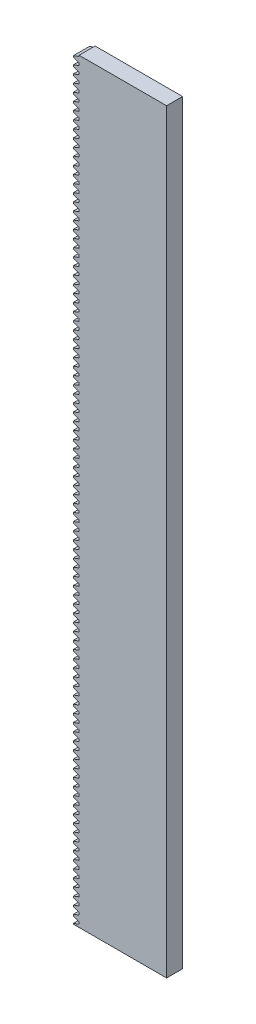
SolidWorks part; units mm, degrees
ref_plane "Front Plane" through (0, 0, 0) normal (0, 0, 1) x (1, 0, 0)
ref_plane "Top Plane" through (0, 0, 0) normal (0, 1, 0) x (1, 0, 0)
ref_plane "Right Plane" through (0, 0, 0) normal (1, 0, 0) x (0, 0, -1)
sketch "Sketch1" plane through (0, 0, 0) normal (0, 0, 1) x (1, 0, 0)
  line L0 (-9.5, -73.594) -> (-8.375, -74.0034)
  line L1 (-9, -75) -> (9, -75) construction
  line L2 (-9, -75) -> (-9, 75) construction
  line L3 (-9, 75) -> (9, 75) construction
  line L4 (9, -75) -> (9, 75) construction
  line L5 (-9, -75) -> (9, 75) construction
  line L6 (-9, 75) -> (9, -75) construction
  line L7 (-8.375, -74.0034) -> (-8.375, -74.4479)
  line L8 (-8.375, -74.4479) -> (-9.5, -74.8573)
  line L9 (-9.5, -74.8573) -> (-9.5, -75)
  line L10 (-9.5, -75) -> (9, -75)
  line L11 (9, -75) -> (9, 75)
  line L12 (9, 75) -> (-8.375, 75)
  line L13 (-8.375, 75) -> (-8.375, 74.7778)
  line L14 (-8.375, 74.7778) -> (-9.5, 74.3683)
  line L15 (-9.5, 74.3683) -> (-9.5, 74.0609)
  line L16 (-9.5, 74.0609) -> (-8.375, 73.6514)
  line L17 (-8.375, 73.6514) -> (-8.375, 73.207)
  line L18 (-8.375, 73.207) -> (-9.5, 72.7975)
  line L19 (-9.5, 72.7975) -> (-9.5, 72.4901)
  line L20 (-9.5, 72.4901) -> (-8.375, 72.0806)
  line L21 (-8.375, 72.0806) -> (-8.375, 71.6362)
  line L22 (-8.375, 71.6362) -> (-9.5, 71.2267)
  line L23 (-9.5, 71.2267) -> (-9.5, 70.9193)
  line L24 (-9.5, 70.9193) -> (-8.375, 70.5098)
  line L25 (-8.375, 70.5098) -> (-8.375, 70.0654)
  line L26 (-8.375, 70.0654) -> (-9.5, 69.6559)
  line L27 (-9.5, 69.6559) -> (-9.5, 69.3485)
  line L28 (-9.5, 69.3485) -> (-8.375, 68.939)
  line L29 (-8.375, 68.939) -> (-8.375, 68.4946)
  line L30 (-8.375, 68.4946) -> (-9.5, 68.0851)
  line L31 (-9.5, 68.0851) -> (-9.5, 67.7777)
  line L32 (-9.5, 67.7777) -> (-8.375, 67.3682)
  line L33 (-8.375, 67.3682) -> (-8.375, 66.9238)
  line L34 (-8.375, 66.9238) -> (-9.5, 66.5143)
  line L35 (-9.5, 66.5143) -> (-9.5, 66.2069)
  line L36 (-9.5, 66.2069) -> (-8.375, 65.7974)
  line L37 (-8.375, 65.7974) -> (-8.375, 65.353)
  line L38 (-8.375, 65.353) -> (-9.5, 64.9435)
  line L39 (-9.5, 64.9435) -> (-9.5, 64.6361)
  line L40 (-9.5, 64.6361) -> (-8.375, 64.2266)
  line L41 (-8.375, 64.2266) -> (-8.375, 63.7822)
  line L42 (-8.375, 63.7822) -> (-9.5, 63.3727)
  line L43 (-9.5, 63.3727) -> (-9.5, 63.0653)
  line L44 (-9.5, 63.0653) -> (-8.375, 62.6558)
  line L45 (-8.375, 62.6558) -> (-8.375, 62.2114)
  line L46 (-8.375, 62.2114) -> (-9.5, 61.8019)
  line L47 (-9.5, 61.8019) -> (-9.5, 61.4945)
  line L48 (-9.5, 61.4945) -> (-8.375, 61.0851)
  line L49 (-8.375, 61.0851) -> (-8.375, 60.6406)
  line L50 (-8.375, 60.6406) -> (-9.5, 60.2311)
  line L51 (-9.5, 60.2311) -> (-9.5, 59.9237)
  line L52 (-9.5, 59.9237) -> (-8.375, 59.5143)
  line L53 (-8.375, 59.5143) -> (-8.375, 59.0698)
  line L54 (-8.375, 59.0698) -> (-9.5, 58.6604)
  line L55 (-9.5, 58.6604) -> (-9.5, 58.3529)
  line L56 (-9.5, 58.3529) -> (-8.375, 57.9435)
  line L57 (-8.375, 57.9435) -> (-8.375, 57.499)
  line L58 (-8.375, 57.499) -> (-9.5, 57.0896)
  line L59 (-9.5, 57.0896) -> (-9.5, 56.7821)
  line L60 (-9.5, 56.7821) -> (-8.375, 56.3727)
  line L61 (-8.375, 56.3727) -> (-8.375, 55.9282)
  line L62 (-8.375, 55.9282) -> (-9.5, 55.5188)
  line L63 (-9.5, 55.5188) -> (-9.5, 55.2113)
  line L64 (-9.5, 55.2113) -> (-8.375, 54.8019)
  line L65 (-8.375, 54.8019) -> (-8.375, 54.3574)
  line L66 (-8.375, 54.3574) -> (-9.5, 53.948)
  line L67 (-9.5, 53.948) -> (-9.5, 53.6405)
  line L68 (-9.5, 53.6405) -> (-8.375, 53.2311)
  line L69 (-8.375, 53.2311) -> (-8.375, 52.7866)
  line L70 (-8.375, 52.7866) -> (-9.5, 52.3772)
  line L71 (-9.5, 52.3772) -> (-9.5, 52.0697)
  line L72 (-9.5, 52.0697) -> (-8.375, 51.6603)
  line L73 (-8.375, 51.6603) -> (-8.375, 51.2158)
  line L74 (-8.375, 51.2158) -> (-9.5, 50.8064)
  line L75 (-9.5, 50.8064) -> (-9.5, 50.4989)
  line L76 (-9.5, 50.4989) -> (-8.375, 50.0895)
  line L77 (-8.375, 50.0895) -> (-8.375, 49.645)
  line L78 (-8.375, 49.645) -> (-9.5, 49.2356)
  line L79 (-9.5, 49.2356) -> (-9.5, 48.9281)
  line L80 (-9.5, 48.9281) -> (-8.375, 48.5187)
  line L81 (-8.375, 48.5187) -> (-8.375, 48.0742)
  line L82 (-8.375, 48.0742) -> (-9.5, 47.6648)
  line L83 (-9.5, 47.6648) -> (-9.5, 47.3574)
  line L84 (-9.5, 47.3574) -> (-8.375, 46.9479)
  line L85 (-8.375, 46.9479) -> (-8.375, 46.5034)
  line L86 (-8.375, 46.5034) -> (-9.5, 46.094)
  line L87 (-9.5, 46.094) -> (-9.5, 45.7866)
  line L88 (-9.5, 45.7866) -> (-8.375, 45.3771)
  line L89 (-8.375, 45.3771) -> (-8.375, 44.9327)
  line L90 (-8.375, 44.9327) -> (-9.5, 44.5232)
  line L91 (-9.5, 44.5232) -> (-9.5, 44.2158)
  line L92 (-9.5, 44.2158) -> (-8.375, 43.8063)
  line L93 (-8.375, 43.8063) -> (-8.375, 43.3619)
  line L94 (-8.375, 43.3619) -> (-9.5, 42.9524)
  line L95 (-9.5, 42.9524) -> (-9.5, 42.645)
  line L96 (-9.5, 42.645) -> (-8.375, 42.2355)
  line L97 (-8.375, 42.2355) -> (-8.375, 41.7911)
  line L98 (-8.375, 41.7911) -> (-9.5, 41.3816)
  line L99 (-9.5, 41.3816) -> (-9.5, 41.0742)
  line L100 (-9.5, 41.0742) -> (-8.375, 40.6647)
  line L101 (-8.375, 40.6647) -> (-8.375, 40.2203)
  line L102 (-8.375, 40.2203) -> (-9.5, 39.8108)
  line L103 (-9.5, 39.8108) -> (-9.5, 39.5034)
  line L104 (-9.5, 39.5034) -> (-8.375, 39.0939)
  line L105 (-8.375, 39.0939) -> (-8.375, 38.6495)
  line L106 (-8.375, 38.6495) -> (-9.5, 38.24)
  line L107 (-9.5, 38.24) -> (-9.5, 37.9326)
  line L108 (-9.5, 37.9326) -> (-8.375, 37.5231)
  line L109 (-8.375, 37.5231) -> (-8.375, 37.0787)
  line L110 (-8.375, 37.0787) -> (-9.5, 36.6692)
  line L111 (-9.5, 36.6692) -> (-9.5, 36.3618)
  line L112 (-9.5, 36.3618) -> (-8.375, 35.9523)
  line L113 (-8.375, 35.9523) -> (-8.375, 35.5079)
  line L114 (-8.375, 35.5079) -> (-9.5, 35.0984)
  line L115 (-9.5, 35.0984) -> (-9.5, 34.791)
  line L116 (-9.5, 34.791) -> (-8.375, 34.3815)
  line L117 (-8.375, 34.3815) -> (-8.375, 33.9371)
  line L118 (-8.375, 33.9371) -> (-9.5, 33.5276)
  line L119 (-9.5, 33.5276) -> (-9.5, 33.2202)
  line L120 (-9.5, 33.2202) -> (-8.375, 32.8107)
  line L121 (-8.375, 32.8107) -> (-8.375, 32.3663)
  line L122 (-8.375, 32.3663) -> (-9.5, 31.9568)
  line L123 (-9.5, 31.9568) -> (-9.5, 31.6494)
  line L124 (-9.5, 31.6494) -> (-8.375, 31.2399)
  line L125 (-8.375, 31.2399) -> (-8.375, 30.7955)
  line L126 (-8.375, 30.7955) -> (-9.5, 30.386)
  line L127 (-9.5, 30.386) -> (-9.5, 30.0786)
  line L128 (-9.5, 30.0786) -> (-8.375, 29.6691)
  line L129 (-8.375, 29.6691) -> (-8.375, 29.2247)
  line L130 (-8.375, 29.2247) -> (-9.5, 28.8152)
  line L131 (-9.5, 28.8152) -> (-9.5, 28.5078)
  line L132 (-9.5, 28.5078) -> (-8.375, 28.0983)
  line L133 (-8.375, 28.0983) -> (-8.375, 27.6539)
  line L134 (-8.375, 27.6539) -> (-9.5, 27.2444)
  line L135 (-9.5, 27.2444) -> (-9.5, 26.937)
  line L136 (-9.5, 26.937) -> (-8.375, 26.5275)
  line L137 (-8.375, 26.5275) -> (-8.375, 26.0831)
  line L138 (-8.375, 26.0831) -> (-9.5, 25.6736)
  line L139 (-9.5, 25.6736) -> (-9.5, 25.3662)
  line L140 (-9.5, 25.3662) -> (-8.375, 24.9567)
  line L141 (-8.375, 24.9567) -> (-8.375, 24.5123)
  line L142 (-8.375, 24.5123) -> (-9.5, 24.1028)
  line L143 (-9.5, 24.1028) -> (-9.5, 23.7954)
  line L144 (-9.5, 23.7954) -> (-8.375, 23.3859)
  line L145 (-8.375, 23.3859) -> (-8.375, 22.9415)
  line L146 (-8.375, 22.9415) -> (-9.5, 22.532)
  line L147 (-9.5, 22.532) -> (-9.5, 22.2246)
  line L148 (-9.5, 22.2246) -> (-8.375, 21.8151)
  line L149 (-8.375, 21.8151) -> (-8.375, 21.3707)
  line L150 (-8.375, 21.3707) -> (-9.5, 20.9612)
  line L151 (-9.5, 20.9612) -> (-9.5, 20.6538)
  line L152 (-9.5, 20.6538) -> (-8.375, 20.2443)
  line L153 (-8.375, 20.2443) -> (-8.375, 19.7999)
  line L154 (-8.375, 19.7999) -> (-9.5, 19.3904)
  line L155 (-9.5, 19.3904) -> (-9.5, 19.083)
  line L156 (-9.5, 19.083) -> (-8.375, 18.6735)
  line L157 (-8.375, 18.6735) -> (-8.375, 18.2291)
  line L158 (-8.375, 18.2291) -> (-9.5, 17.8196)
  line L159 (-9.5, 17.8196) -> (-9.5, 17.5122)
  line L160 (-9.5, 17.5122) -> (-8.375, 17.1028)
  line L161 (-8.375, 17.1028) -> (-8.375, 16.6583)
  line L162 (-8.375, 16.6583) -> (-9.5, 16.2489)
  line L163 (-9.5, 16.2489) -> (-9.5, 15.9414)
  line L164 (-9.5, 15.9414) -> (-8.375, 15.532)
  line L165 (-8.375, 15.532) -> (-8.375, 15.0875)
  line L166 (-8.375, 15.0875) -> (-9.5, 14.6781)
  line L167 (-9.5, 14.6781) -> (-9.5, 14.3706)
  line L168 (-9.5, 14.3706) -> (-8.375, 13.9612)
  line L169 (-8.375, 13.9612) -> (-8.375, 13.5167)
  line L170 (-8.375, 13.5167) -> (-9.5, 13.1073)
  line L171 (-9.5, 13.1073) -> (-9.5, 12.7998)
  line L172 (-9.5, 12.7998) -> (-8.375, 12.3904)
  line L173 (-8.375, 12.3904) -> (-8.375, 11.9459)
  line L174 (-8.375, 11.9459) -> (-9.5, 11.5365)
  line L175 (-9.5, 11.5365) -> (-9.5, 11.229)
  line L176 (-9.5, 11.229) -> (-8.375, 10.8196)
  line L177 (-8.375, 10.8196) -> (-8.375, 10.3751)
  line L178 (-8.375, 10.3751) -> (-9.5, 9.9657)
  line L179 (-9.5, 9.9657) -> (-9.5, 9.6582)
  line L180 (-9.5, 9.6582) -> (-8.375, 9.2488)
  line L181 (-8.375, 9.2488) -> (-8.375, 8.8043)
  line L182 (-8.375, 8.8043) -> (-9.5, 8.3949)
  line L183 (-9.5, 8.3949) -> (-9.5, 8.0874)
  line L184 (-9.5, 8.0874) -> (-8.375, 7.678)
  line L185 (-8.375, 7.678) -> (-8.375, 7.2335)
  line L186 (-8.375, 7.2335) -> (-9.5, 6.8241)
  line L187 (-9.5, 6.8241) -> (-9.5, 6.5166)
  line L188 (-9.5, 6.5166) -> (-8.375, 6.1072)
  line L189 (-8.375, 6.1072) -> (-8.375, 5.6627)
  line L190 (-8.375, 5.6627) -> (-9.5, 5.2533)
  line L191 (-9.5, 5.2533) -> (-9.5, 4.9458)
  line L192 (-9.5, 4.9458) -> (-8.375, 4.5364)
  line L193 (-8.375, 4.5364) -> (-8.375, 4.0919)
  line L194 (-8.375, 4.0919) -> (-9.5, 3.6825)
  line L195 (-9.5, 3.6825) -> (-9.5, 3.3751)
  line L196 (-9.5, 3.3751) -> (-8.375, 2.9656)
  line L197 (-8.375, 2.9656) -> (-8.375, 2.5212)
  line L198 (-8.375, 2.5212) -> (-9.5, 2.1117)
  line L199 (-9.5, 2.1117) -> (-9.5, 1.8043)
  line L200 (-9.5, 1.8043) -> (-8.375, 1.3948)
  line L201 (-8.375, 1.3948) -> (-8.375, 0.9504)
  line L202 (-8.375, 0.9504) -> (-9.5, 0.5409)
  line L203 (-9.5, 0.5409) -> (-9.5, 0.2335)
  line L204 (-9.5, 0.2335) -> (-8.375, -0.176)
  line L205 (-8.375, -0.176) -> (-8.375, -0.6204)
  line L206 (-8.375, -0.6204) -> (-9.5, -1.0299)
  line L207 (-9.5, -1.0299) -> (-9.5, -1.3373)
  line L208 (-9.5, -1.3373) -> (-8.375, -1.7468)
  line L209 (-8.375, -1.7468) -> (-8.375, -2.1912)
  line L210 (-8.375, -2.1912) -> (-9.5, -2.6007)
  line L211 (-9.5, -2.6007) -> (-9.5, -2.9081)
  line L212 (-9.5, -2.9081) -> (-8.375, -3.3176)
  line L213 (-8.375, -3.3176) -> (-8.375, -3.762)
  line L214 (-8.375, -3.762) -> (-9.5, -4.1715)
  line L215 (-9.5, -4.1715) -> (-9.5, -4.4789)
  line L216 (-9.5, -4.4789) -> (-8.375, -4.8884)
  line L217 (-8.375, -4.8884) -> (-8.375, -5.3328)
  line L218 (-8.375, -5.3328) -> (-9.5, -5.7423)
  line L219 (-9.5, -5.7423) -> (-9.5, -6.0497)
  line L220 (-9.5, -6.0497) -> (-8.375, -6.4592)
  line L221 (-8.375, -6.4592) -> (-8.375, -6.9036)
  line L222 (-8.375, -6.9036) -> (-9.5, -7.3131)
  line L223 (-9.5, -7.3131) -> (-9.5, -7.6205)
  line L224 (-9.5, -7.6205) -> (-8.375, -8.03)
  line L225 (-8.375, -8.03) -> (-8.375, -8.4744)
  line L226 (-8.375, -8.4744) -> (-9.5, -8.8839)
  line L227 (-9.5, -8.8839) -> (-9.5, -9.1913)
  line L228 (-9.5, -9.1913) -> (-8.375, -9.6008)
  line L229 (-8.375, -9.6008) -> (-8.375, -10.0452)
  line L230 (-8.375, -10.0452) -> (-9.5, -10.4547)
  line L231 (-9.5, -10.4547) -> (-9.5, -10.7621)
  line L232 (-9.5, -10.7621) -> (-8.375, -11.1716)
  line L233 (-8.375, -11.1716) -> (-8.375, -11.616)
  line L234 (-8.375, -11.616) -> (-9.5, -12.0255)
  line L235 (-9.5, -12.0255) -> (-9.5, -12.3329)
  line L236 (-9.5, -12.3329) -> (-8.375, -12.7424)
  line L237 (-8.375, -12.7424) -> (-8.375, -13.1868)
  line L238 (-8.375, -13.1868) -> (-9.5, -13.5963)
  line L239 (-9.5, -13.5963) -> (-9.5, -13.9037)
  line L240 (-9.5, -13.9037) -> (-8.375, -14.3132)
  line L241 (-8.375, -14.3132) -> (-8.375, -14.7576)
  line L242 (-8.375, -14.7576) -> (-9.5, -15.1671)
  line L243 (-9.5, -15.1671) -> (-9.5, -15.4745)
  line L244 (-9.5, -15.4745) -> (-8.375, -15.884)
  line L245 (-8.375, -15.884) -> (-8.375, -16.3284)
  line L246 (-8.375, -16.3284) -> (-9.5, -16.7379)
  line L247 (-9.5, -16.7379) -> (-9.5, -17.0453)
  line L248 (-9.5, -17.0453) -> (-8.375, -17.4548)
  line L249 (-8.375, -17.4548) -> (-8.375, -17.8992)
  line L250 (-8.375, -17.8992) -> (-9.5, -18.3087)
  line L251 (-9.5, -18.3087) -> (-9.5, -18.6161)
  line L252 (-9.5, -18.6161) -> (-8.375, -19.0256)
  line L253 (-8.375, -19.0256) -> (-8.375, -19.47)
  line L254 (-8.375, -19.47) -> (-9.5, -19.8795)
  line L255 (-9.5, -19.8795) -> (-9.5, -20.1869)
  line L256 (-9.5, -20.1869) -> (-8.375, -20.5964)
  line L257 (-8.375, -20.5964) -> (-8.375, -21.0408)
  line L258 (-8.375, -21.0408) -> (-9.5, -21.4503)
  line L259 (-9.5, -21.4503) -> (-9.5, -21.7577)
  line L260 (-9.5, -21.7577) -> (-8.375, -22.1672)
  line L261 (-8.375, -22.1672) -> (-8.375, -22.6116)
  line L262 (-8.375, -22.6116) -> (-9.5, -23.0211)
  line L263 (-9.5, -23.0211) -> (-9.5, -23.3285)
  line L264 (-9.5, -23.3285) -> (-8.375, -23.738)
  line L265 (-8.375, -23.738) -> (-8.375, -24.1824)
  line L266 (-8.375, -24.1824) -> (-9.5, -24.5919)
  line L267 (-9.5, -24.5919) -> (-9.5, -24.8993)
  line L268 (-9.5, -24.8993) -> (-8.375, -25.3087)
  line L269 (-8.375, -25.3087) -> (-8.375, -25.7532)
  line L270 (-8.375, -25.7532) -> (-9.5, -26.1626)
  line L271 (-9.5, -26.1626) -> (-9.5, -26.4701)
  line L272 (-9.5, -26.4701) -> (-8.375, -26.8795)
  line L273 (-8.375, -26.8795) -> (-8.375, -27.324)
  line L274 (-8.375, -27.324) -> (-9.5, -27.7334)
  line L275 (-9.5, -27.7334) -> (-9.5, -28.0409)
  line L276 (-9.5, -28.0409) -> (-8.375, -28.4503)
  line L277 (-8.375, -28.4503) -> (-8.375, -28.8948)
  line L278 (-8.375, -28.8948) -> (-9.5, -29.3042)
  line L279 (-9.5, -29.3042) -> (-9.5, -29.6117)
  line L280 (-9.5, -29.6117) -> (-8.375, -30.0211)
  line L281 (-8.375, -30.0211) -> (-8.375, -30.4656)
  line L282 (-8.375, -30.4656) -> (-9.5, -30.875)
  line L283 (-9.5, -30.875) -> (-9.5, -31.1825)
  line L284 (-9.5, -31.1825) -> (-8.375, -31.5919)
  line L285 (-8.375, -31.5919) -> (-8.375, -32.0364)
  line L286 (-8.375, -32.0364) -> (-9.5, -32.4458)
  line L287 (-9.5, -32.4458) -> (-9.5, -32.7533)
  line L288 (-9.5, -32.7533) -> (-8.375, -33.1627)
  line L289 (-8.375, -33.1627) -> (-8.375, -33.6072)
  line L290 (-8.375, -33.6072) -> (-9.5, -34.0166)
  line L291 (-9.5, -34.0166) -> (-9.5, -34.3241)
  line L292 (-9.5, -34.3241) -> (-8.375, -34.7335)
  line L293 (-8.375, -34.7335) -> (-8.375, -35.178)
  line L294 (-8.375, -35.178) -> (-9.5, -35.5874)
  line L295 (-9.5, -35.5874) -> (-9.5, -35.8949)
  line L296 (-9.5, -35.8949) -> (-8.375, -36.3043)
  line L297 (-8.375, -36.3043) -> (-8.375, -36.7488)
  line L298 (-8.375, -36.7488) -> (-9.5, -37.1582)
  line L299 (-9.5, -37.1582) -> (-9.5, -37.4657)
  line L300 (-9.5, -37.4657) -> (-8.375, -37.8751)
  line L301 (-8.375, -37.8751) -> (-8.375, -38.3196)
  line L302 (-8.375, -38.3196) -> (-9.5, -38.729)
  line L303 (-9.5, -38.729) -> (-9.5, -39.0364)
  line L304 (-9.5, -39.0364) -> (-8.375, -39.4459)
  line L305 (-8.375, -39.4459) -> (-8.375, -39.8903)
  line L306 (-8.375, -39.8903) -> (-9.5, -40.2998)
  line L307 (-9.5, -40.2998) -> (-9.5, -40.6072)
  line L308 (-9.5, -40.6072) -> (-8.375, -41.0167)
  line L309 (-8.375, -41.0167) -> (-8.375, -41.4611)
  line L310 (-8.375, -41.4611) -> (-9.5, -41.8706)
  line L311 (-9.5, -41.8706) -> (-9.5, -42.178)
  line L312 (-9.5, -42.178) -> (-8.375, -42.5875)
  line L313 (-8.375, -42.5875) -> (-8.375, -43.0319)
  line L314 (-8.375, -43.0319) -> (-9.5, -43.4414)
  line L315 (-9.5, -43.4414) -> (-9.5, -43.7488)
  line L316 (-9.5, -43.7488) -> (-8.375, -44.1583)
  line L317 (-8.375, -44.1583) -> (-8.375, -44.6027)
  line L318 (-8.375, -44.6027) -> (-9.5, -45.0122)
  line L319 (-9.5, -45.0122) -> (-9.5, -45.3196)
  line L320 (-9.5, -45.3196) -> (-8.375, -45.7291)
  line L321 (-8.375, -45.7291) -> (-8.375, -46.1735)
  line L322 (-8.375, -46.1735) -> (-9.5, -46.583)
  line L323 (-9.5, -46.583) -> (-9.5, -46.8904)
  line L324 (-9.5, -46.8904) -> (-8.375, -47.2999)
  line L325 (-8.375, -47.2999) -> (-8.375, -47.7443)
  line L326 (-8.375, -47.7443) -> (-9.5, -48.1538)
  line L327 (-9.5, -48.1538) -> (-9.5, -48.4612)
  line L328 (-9.5, -48.4612) -> (-8.375, -48.8707)
  line L329 (-8.375, -48.8707) -> (-8.375, -49.3151)
  line L330 (-8.375, -49.3151) -> (-9.5, -49.7246)
  line L331 (-9.5, -49.7246) -> (-9.5, -50.032)
  line L332 (-9.5, -50.032) -> (-8.375, -50.4415)
  line L333 (-8.375, -50.4415) -> (-8.375, -50.8859)
  line L334 (-8.375, -50.8859) -> (-9.5, -51.2954)
  line L335 (-9.5, -51.2954) -> (-9.5, -51.6028)
  line L336 (-9.5, -51.6028) -> (-8.375, -52.0123)
  line L337 (-8.375, -52.0123) -> (-8.375, -52.4567)
  line L338 (-8.375, -52.4567) -> (-9.5, -52.8662)
  line L339 (-9.5, -52.8662) -> (-9.5, -53.1736)
  line L340 (-9.5, -53.1736) -> (-8.375, -53.5831)
  line L341 (-8.375, -53.5831) -> (-8.375, -54.0275)
  line L342 (-8.375, -54.0275) -> (-9.5, -54.437)
  line L343 (-9.5, -54.437) -> (-9.5, -54.7444)
  line L344 (-9.5, -54.7444) -> (-8.375, -55.1539)
  line L345 (-8.375, -55.1539) -> (-8.375, -55.5983)
  line L346 (-8.375, -55.5983) -> (-9.5, -56.0078)
  line L347 (-9.5, -56.0078) -> (-9.5, -56.3152)
  line L348 (-9.5, -56.3152) -> (-8.375, -56.7247)
  line L349 (-8.375, -56.7247) -> (-8.375, -57.1691)
  line L350 (-8.375, -57.1691) -> (-9.5, -57.5786)
  line L351 (-9.5, -57.5786) -> (-9.5, -57.886)
  line L352 (-9.5, -57.886) -> (-8.375, -58.2955)
  line L353 (-8.375, -58.2955) -> (-8.375, -58.7399)
  line L354 (-8.375, -58.7399) -> (-9.5, -59.1494)
  line L355 (-9.5, -59.1494) -> (-9.5, -59.4568)
  line L356 (-9.5, -59.4568) -> (-8.375, -59.8663)
  line L357 (-8.375, -59.8663) -> (-8.375, -60.3107)
  line L358 (-8.375, -60.3107) -> (-9.5, -60.7202)
  line L359 (-9.5, -60.7202) -> (-9.5, -61.0276)
  line L360 (-9.5, -61.0276) -> (-8.375, -61.4371)
  line L361 (-8.375, -61.4371) -> (-8.375, -61.8815)
  line L362 (-8.375, -61.8815) -> (-9.5, -62.291)
  line L363 (-9.5, -62.291) -> (-9.5, -62.5984)
  line L364 (-9.5, -62.5984) -> (-8.375, -63.0079)
  line L365 (-8.375, -63.0079) -> (-8.375, -63.4523)
  line L366 (-8.375, -63.4523) -> (-9.5, -63.8618)
  line L367 (-9.5, -63.8618) -> (-9.5, -64.1692)
  line L368 (-9.5, -64.1692) -> (-8.375, -64.5787)
  line L369 (-8.375, -64.5787) -> (-8.375, -65.0231)
  line L370 (-8.375, -65.0231) -> (-9.5, -65.4326)
  line L371 (-9.5, -65.4326) -> (-9.5, -65.74)
  line L372 (-9.5, -65.74) -> (-8.375, -66.1495)
  line L373 (-8.375, -66.1495) -> (-8.375, -66.5939)
  line L374 (-8.375, -66.5939) -> (-9.5, -67.0034)
  line L375 (-9.5, -67.0034) -> (-9.5, -67.3108)
  line L376 (-9.5, -67.3108) -> (-8.375, -67.7202)
  line L377 (-8.375, -67.7202) -> (-8.375, -68.1647)
  line L378 (-8.375, -68.1647) -> (-9.5, -68.5741)
  line L379 (-9.5, -68.5741) -> (-9.5, -68.8816)
  line L380 (-9.5, -68.8816) -> (-8.375, -69.291)
  line L381 (-8.375, -69.291) -> (-8.375, -69.7355)
  line L382 (-8.375, -69.7355) -> (-9.5, -70.1449)
  line L383 (-9.5, -70.1449) -> (-9.5, -70.4524)
  line L384 (-9.5, -70.4524) -> (-8.375, -70.8618)
  line L385 (-8.375, -70.8618) -> (-8.375, -71.3063)
  line L386 (-8.375, -71.3063) -> (-9.5, -71.7157)
  line L387 (-9.5, -71.7157) -> (-9.5, -72.0232)
  line L388 (-9.5, -72.0232) -> (-8.375, -72.4326)
  line L389 (-8.375, -72.4326) -> (-8.375, -72.8771)
  line L390 (-8.375, -72.8771) -> (-9.5, -73.2865)
  line L391 (-9.5, -73.2865) -> (-9.5, -73.594)
  point P0 (0, 0)
  dimension "D1" = 18
  dimension "D2" = 150
extrude "Boss-Extrude1" add sketch "Sketch1" along normal blind 3.175
